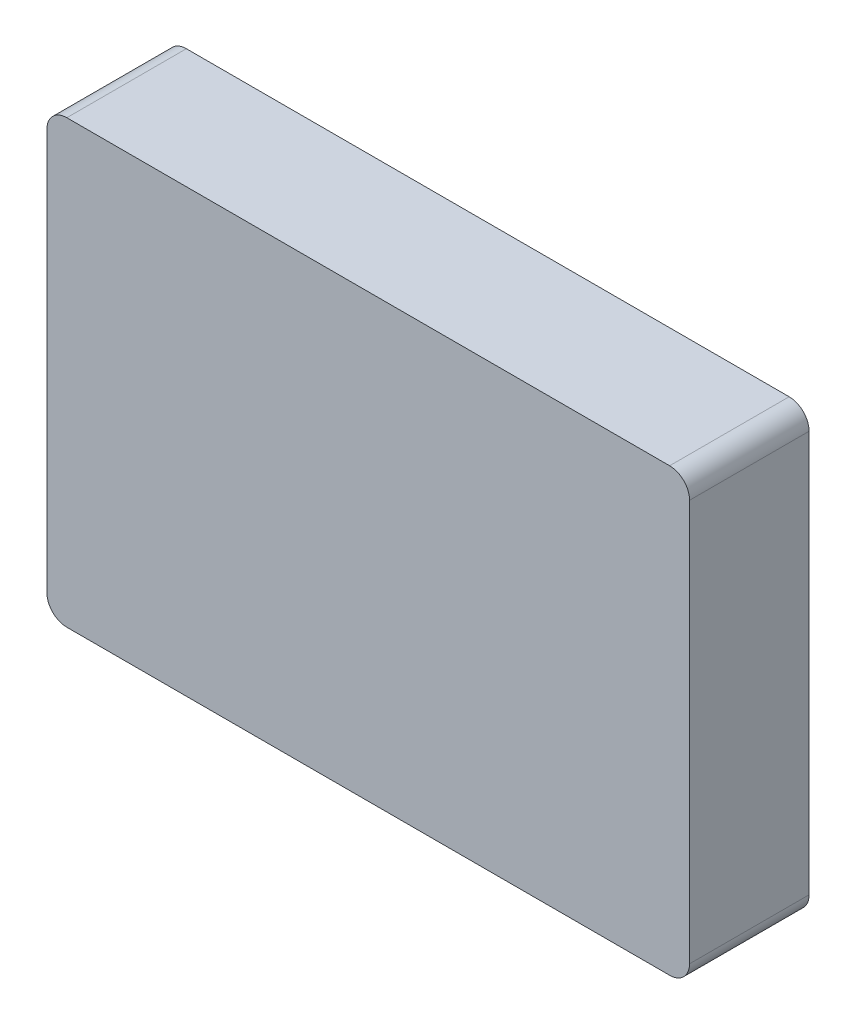
SolidWorks part; units mm, degrees
ref_plane "前视基准面" through (0, 0, 0) normal (0, 0, 1) x (1, 0, 0)
ref_plane "上视基准面" through (0, 0, 0) normal (0, 1, 0) x (1, 0, 0)
ref_plane "右视基准面" through (0, 0, 0) normal (1, 0, 0) x (0, 0, -1)
sketch "草图1" plane through (0, 0, 0) normal (0, 0, 1) x (1, 0, 0)
  line L0 (-46.7234, -29.7816) -> (27.9274, -29.7816) construction
  line L1 (-46.7234, -5.0927) -> (-46.7234, -54.4704) construction
  line L2 (27.9274, -44.5935) -> (27.9274, -5.0927) construction
  circle A0 centre (-25.174, -5.08) radius 2.5
  circle A2 centre (-25.174, -54.4831) radius 2.5
  circle A3 centre (27.9401, -46.1934) radius 2.5
extrude "凸台-拉伸1" add sketch "草图1" along normal blind 2.5
sketch "草图2" plane through (0, 0, 0) normal (0, 0, -1) x (-1, 0, 0)
  circle A0 centre (25.174, -5.08) radius 1.5
  circle A1 centre (25.174, -54.4831) radius 1.5
  circle A2 centre (-27.9401, -46.1934) radius 1.5
  dimension "D1" = 3
extrude "凸台-拉伸2" add sketch "草图2" along normal blind 2.5
sketch "草图3" plane through (0, 0, 0) normal (0, 0, -1) x (-1, 0, 0)
  line L1 (-8.0015, -26.6968) -> (-2.9409, -26.6968)
  line L2 (-8.0015, -26.6968) -> (-8.0015, -13.083)
  line L3 (-8.0015, -13.083) -> (-2.9409, -13.083)
  line L4 (-2.9409, -26.6968) -> (-2.9409, -13.083)
  line L5 (-8.0015, -26.6968) -> (-2.9409, -13.083) construction
  line L6 (-8.0015, -13.083) -> (-2.9409, -26.6968) construction
  point P0 (-5.4712, -19.8899)
extrude "凸台-拉伸3" add sketch "草图3" against normal blind 2.5 separate body
sketch "草图4" plane through (0, 0, 2.5) normal (0, 0, 1) x (1, 0, 0)
  line L1 (-49.7234, -2.0927) -> (30.9274, -2.0927)
  line L2 (-49.7234, -2.0927) -> (-49.7234, -57.4704)
  line L3 (-49.7234, -57.4704) -> (30.9274, -57.4704)
  line L4 (30.9274, -2.0927) -> (30.9274, -57.4704)
extrude "凸台-拉伸4" add sketch "草图4" along normal blind 2
sketch "草图5" plane through (0, 0, 2.5) normal (0, 0, -1) x (-1, 0, 0)
  line L0 (47.2234, -54.9704) -> (47.2234, -4.5927)
  line L1 (47.2234, -4.5927) -> (-28.4274, -4.5927)
  line L2 (-28.4274, -4.5927) -> (-28.4274, -54.9704)
  line L3 (-28.4274, -54.9704) -> (47.2234, -54.9704)
  line L4 (49.7234, -57.4704) -> (49.7234, -2.0927)
  line L5 (49.7234, -2.0927) -> (-30.9274, -2.0927)
  line L6 (-30.9274, -2.0927) -> (-30.9274, -57.4704)
  line L7 (-30.9274, -57.4704) -> (49.7234, -57.4704)
  line L8 (49.7234, -57.4704) -> (49.7234, -2.0927)
  line L9 (49.7234, -2.0927) -> (-30.9274, -2.0927)
  line L10 (-30.9274, -2.0927) -> (-30.9274, -57.4704)
  line L11 (-30.9274, -57.4704) -> (49.7234, -57.4704)
  dimension "D1" = 0
  dimension "D2" = 2.5
extrude "凸台-拉伸5" add sketch "草图5" along normal blind 13
fillet "圆角1" radius 2.5 4 edges at (30.9274, -2.0927, -3) (-49.7234, -2.0927, -3) (-49.7234, -57.4704, -3) (30.9274, -57.4704, -3)
sketch "草图7" plane through (0, -57.4704, 0) normal (0, -1, 0) x (1, 0, 0)
  line L0 (-1.6754, -3.0801) -> (-6.1754, -3.0801) construction
  line L1 (-1.6754, -6.5801) -> (-6.1754, -6.5801)
  line L2 (-1.6754, 0.4199) -> (-6.1754, 0.4199)
  arc A0 (-1.6754, -6.5801) -> (-1.6754, 0.4199) centre (-1.6754, -3.0801) ccw
  arc A1 (-6.1754, 0.4199) -> (-6.1754, -6.5801) centre (-6.1754, -3.0801) ccw
  point P2 (-3.9254, -3.0801)
  point P7 (1.8246, -3.0801)
  point P8 (-9.6754, -3.0801)
  point P9 (0, 0)
  dimension "D1" = 7
  dimension "D2" = 11.5
extrude "切除-拉伸1" cut sketch "草图7" against normal blind 2.6
